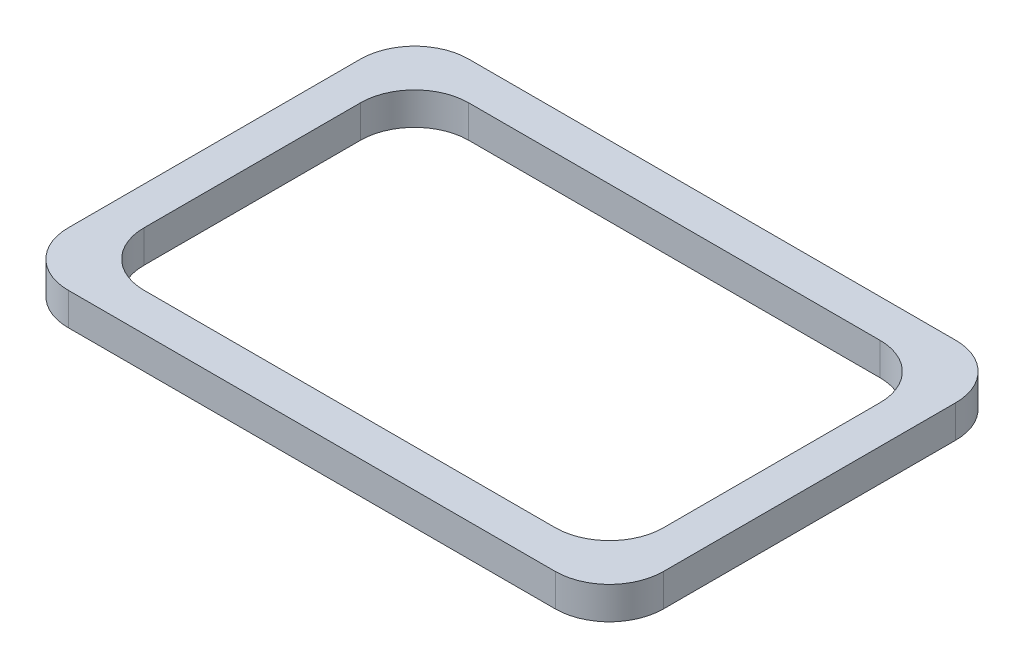
SolidWorks part; units mm, degrees
ref_plane "Front Plane" through (0, 0, 0) normal (0, 0, 1) x (1, 0, 0)
ref_plane "Top Plane" through (0, 0, 0) normal (0, 1, 0) x (1, 0, 0)
ref_plane "Right Plane" through (0, 0, 0) normal (1, 0, 0) x (0, 0, -1)
sketch "Sketch1" plane through (0, 0, 0) normal (0, 1, 0) x (1, 0, 0)
  line L1 (-19, -15) -> (19, -15)
  line L2 (-24, -10) -> (-24, 10)
  line L3 (-19, 15) -> (19, 15)
  line L4 (24, -10) -> (24, 10)
  line L5 (-24, -15) -> (24, 15) construction
  line L6 (-24, 15) -> (24, -15) construction
  line L7 (-22.5, 18.5) -> (22.5, 18.5)
  line L8 (-27.5, 13.5) -> (-27.5, -13.5)
  line L9 (-22.5, -18.5) -> (22.5, -18.5)
  line L10 (27.5, 13.5) -> (27.5, -13.5)
  line L11 (-27.5, 18.5) -> (27.5, -18.5) construction
  line L12 (-27.5, -18.5) -> (27.5, 18.5) construction
  arc A0 (22.5, -18.5) -> (27.5, -13.5) centre (22.5, -13.5) ccw
  arc A1 (22.5, 18.5) -> (27.5, 13.5) centre (22.5, 13.5) cw
  arc A2 (-22.5, 18.5) -> (-27.5, 13.5) centre (-22.5, 13.5) ccw
  arc A3 (-27.5, -13.5) -> (-22.5, -18.5) centre (-22.5, -13.5) ccw
  arc A4 (-19, -15) -> (-24, -10) centre (-19, -10) cw
  arc A5 (19, 15) -> (24, 10) centre (19, 10) cw
  arc A6 (19, -15) -> (24, -10) centre (19, -10) ccw
  arc A7 (-24, 10) -> (-19, 15) centre (-19, 10) cw
  point P0 (0, 0)
  point P5 (0, 0)
  dimension "D5" = 5
  dimension "D1" = 30
  dimension "D2" = 48
  dimension "D3" = 37
  dimension "D4" = 55
extrude "Boss-Extrude1" add sketch "Sketch1" along normal blind 3
